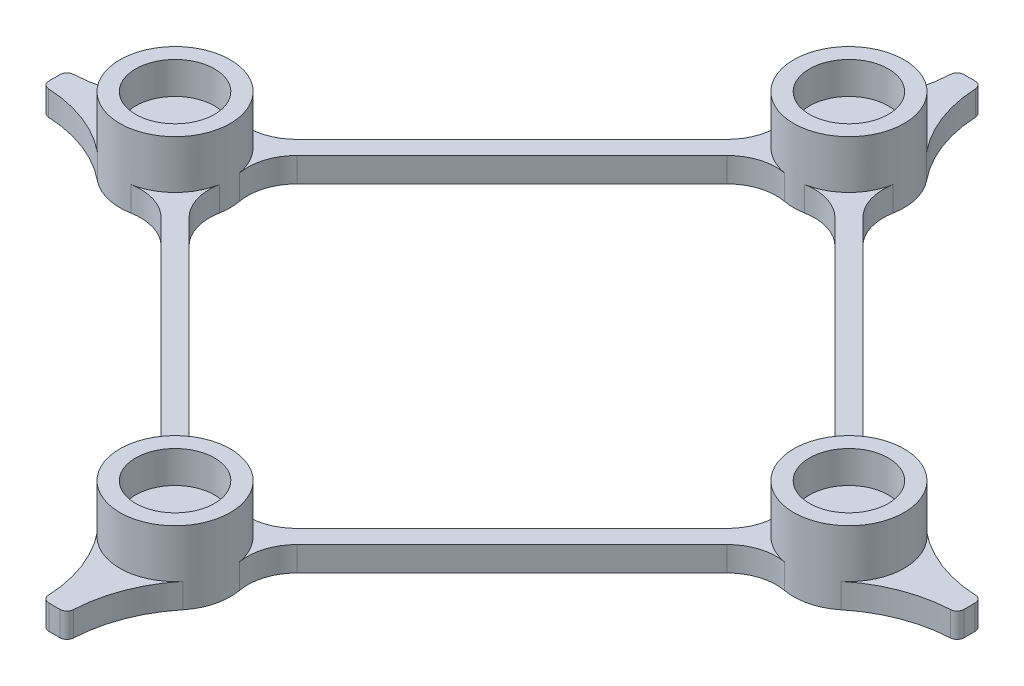
SolidWorks part; units mm, degrees
ref_plane "Front Plane" through (0, 0, 0) normal (0, 0, 1) x (1, 0, 0)
ref_plane "Top Plane" through (0, 0, 0) normal (0, 1, 0) x (1, 0, 0)
ref_plane "Right Plane" through (0, 0, 0) normal (1, 0, 0) x (0, 0, -1)
sketch "Sketch1" plane through (0, 0, 0) normal (0, 1, 0) x (1, 0, 0)
  line L0 (0, 0) -> (0, 68.328) construction
  line L1 (0, 68.328) -> (0, 92.8) construction
  line L3 (-9.2065, 61.9499) -> (-61.9499, 9.2065)
  line L11 (-6.3781, 59.1215) -> (-59.1215, 6.3781)
  line L21 (-21.9505, 74.6939) -> (0, 52.7434) construction
  line L22 (-2.5, 92.7663) -> (-2.5, 82.8896) construction
  line L23 (0, 52.7434) -> (6.3781, 59.1215) construction
  line L24 (59.1215, 6.3781) -> (6.3781, 59.1215)
  line L25 (61.9499, 9.2065) -> (9.2065, 61.9499)
  line L26 (6.3781, -59.1215) -> (59.1215, -6.3781)
  line L27 (9.2065, -61.9499) -> (61.9499, -9.2065)
  line L28 (-59.1215, -6.3781) -> (-6.3781, -59.1215)
  line L29 (-61.9499, -9.2065) -> (-9.2065, -61.9499)
  circle A0 centre (0, 68.328) radius 8
  circle A1 centre (0, 0) radius 92.8 construction
  arc A2 (-2.5, 92.7663) -> (2.5, 92.7663) centre (0, 0) cw
  arc A9 (-6.3781, 59.1215) -> (6.3781, 59.1215) centre (0, 68.328) ccw
  circle A14 centre (0, 68.328) radius 11.2 construction
  arc A15 (-9.2065, 61.9499) -> (-8.6805, 75.4054) centre (0, 68.328) cw
  arc A16 (-8.6805, 75.4054) -> (-2.5, 92.7663) centre (-29.9736, 92.7663) ccw
  arc A17 (9.2065, 61.9499) -> (8.6805, 75.4054) centre (0, 68.328) ccw
  arc A18 (8.6805, 75.4054) -> (2.5, 92.7663) centre (29.9736, 92.7663) cw
  arc A19 (59.1215, 6.3781) -> (59.1215, -6.3781) centre (68.328, 0) ccw
  arc A20 (61.9499, 9.2065) -> (75.4054, 8.6805) centre (68.328, 0) cw
  arc A21 (61.9499, -9.2065) -> (75.4054, -8.6805) centre (68.328, 0) ccw
  arc A22 (75.4054, -8.6805) -> (92.7663, -2.5) centre (92.7663, -29.9736) cw
  arc A23 (75.4054, 8.6805) -> (92.7663, 2.5) centre (92.7663, 29.9736) ccw
  arc A24 (92.7663, 2.5) -> (92.7663, -2.5) centre (0, 0) cw
  circle A25 centre (68.328, 0) radius 8
  arc A26 (6.3781, -59.1215) -> (-6.3781, -59.1215) centre (0, -68.328) ccw
  arc A27 (9.2065, -61.9499) -> (8.6805, -75.4054) centre (0, -68.328) cw
  arc A28 (-9.2065, -61.9499) -> (-8.6805, -75.4054) centre (0, -68.328) ccw
  arc A29 (-8.6805, -75.4054) -> (-2.5, -92.7663) centre (-29.9736, -92.7663) cw
  arc A30 (8.6805, -75.4054) -> (2.5, -92.7663) centre (29.9736, -92.7663) ccw
  arc A31 (2.5, -92.7663) -> (-2.5, -92.7663) centre (0, 0) cw
  circle A32 centre (0, -68.328) radius 8
  arc A33 (-59.1215, -6.3781) -> (-59.1215, 6.3781) centre (-68.328, 0) ccw
  arc A34 (-61.9499, -9.2065) -> (-75.4054, -8.6805) centre (-68.328, 0) cw
  arc A35 (-61.9499, 9.2065) -> (-75.4054, 8.6805) centre (-68.328, 0) ccw
  arc A36 (-75.4054, 8.6805) -> (-92.7663, 2.5) centre (-92.7663, 29.9736) cw
  arc A37 (-75.4054, -8.6805) -> (-92.7663, -2.5) centre (-92.7663, -29.9736) ccw
  arc A38 (-92.7663, -2.5) -> (-92.7663, 2.5) centre (0, 0) cw
  circle A39 centre (-68.328, 0) radius 8
  point P13 (6.0786, 59.421)
  point P14 (8.9291, 62.2273)
  point P15 (0, 0)
  point P22 (7.213, 58.2866)
  point P31 (0, 0)
  point P54 (0, 0)
  point P76 (0, 0)
  dimension "D1" = 16
  dimension "D2" = 185.6
  dimension "D3" = 68.328
  dimension "D7" = 4
  dimension "D5" = 45
  dimension "D8" = 2.5
  dimension "D4" = 3.2
  dimension "D6" = 4
extrude "Boss-Extrude1" add sketch "Sketch1" along normal blind 5 contours A39 | A38 A37 A34 L29 A28 A29 A31 A30 A27 L27 A21 A22 A24 A23 A20 L25 A17 A18 A2 A16 A15 L3 A35 A36 A39 A32 A25 A0 L28 A33 L11 A9 L24 A19 L26 A26 | A32 | A25 | A0 region at (-8.5687, 0, -68.663) region at (0, 0, -68.328) region at (68.328, 0, 0) region at (0, 0, 68.328) region at (-68.328, 0, 0)
fillet "Fillet1" radius 10 16 edges at (9.2065, 2.5, -61.9499) (-9.2065, 2.5, -61.9499) (6.3781, 2.5, -59.1215) (-6.3781, 2.5, -59.1215) (61.9499, 2.5, 9.2065) (61.9499, 2.5, -9.2065) (59.1215, 2.5, -6.3781) (59.1215, 2.5, 6.3781) (9.2065, 2.5, 61.9499) (-9.2065, 2.5, 61.9499) (6.3781, 2.5, 59.1215) (-6.3781, 2.5, 59.1215) (-59.1215, 2.5, -6.3781) (-59.1215, 2.5, 6.3781) (-61.9499, 2.5, 9.2065) (-61.9499, 2.5, -9.2065)
ref_axis "Axis1" through (0, 6.3, 0) along (0, -1, 0)
fillet "Fillet2" radius 1.4 8 edges at (92.7663, 2.5, 2.5) (92.7663, 2.5, -2.5) (2.5, 2.5, 92.7663) (-2.5, 2.5, 92.7663) (-92.7663, 2.5, 2.5) (-92.7663, 2.5, -2.5) (2.5, 2.5, -92.7663) (-2.5, 2.5, -92.7663)
sketch "Sketch2" plane through (0, 0, 0) normal (0, 1, 0) x (1, 0, 0)
  circle A0 centre (-68.328, 0) radius 11.2
  arc A1 (-61.9499, 9.2065) -> (-75.4054, 8.6805) centre (-68.328, 0) ccw construction
  circle A2 centre (-68.328, 0) radius 8
  circle A3 centre (-68.328, 0) radius 8 construction
  circle A4 centre (0, 68.328) radius 8
  circle A5 centre (0, 68.328) radius 11.2
  circle A6 centre (68.328, 0) radius 8
  circle A7 centre (68.328, 0) radius 11.2
  circle A8 centre (0, -68.328) radius 8
  circle A9 centre (0, -68.328) radius 11.2
  point P9 (14.1121, 73.0339)
  point P10 (0, 0)
  point P21 (0, 0)
  dimension "D1" = 4
extrude "Boss-Extrude2" add sketch "Sketch2" along normal blind 8.3 contours A0 A2 | A2 | A4 | A5 A4 | A6 | A7 A6 | A8 | A9 A8 region at (-79.2112, 0, 0) region at (-68.328, 0, 0) region at (0, 0, -68.328) region at (-10.8832, 0, -68.328) region at (68.328, 0, 0) region at (57.4448, 0, 0) region at (0, 0, 68.328) region at (-10.8832, 0, 68.328)
extrude "Boss-Extrude3" add sketch "Sketch2<3>" along normal blind 6.5 from surface starting at face at (-68.328, 8.3, 11.2)
sketch "Sketch2<3>" plane through (0, 0, 0) normal (0, 1, 0) x (1, 0, 0) same geometry as "Sketch2"
equation "\"D2@Sketch1\"=185.6"
